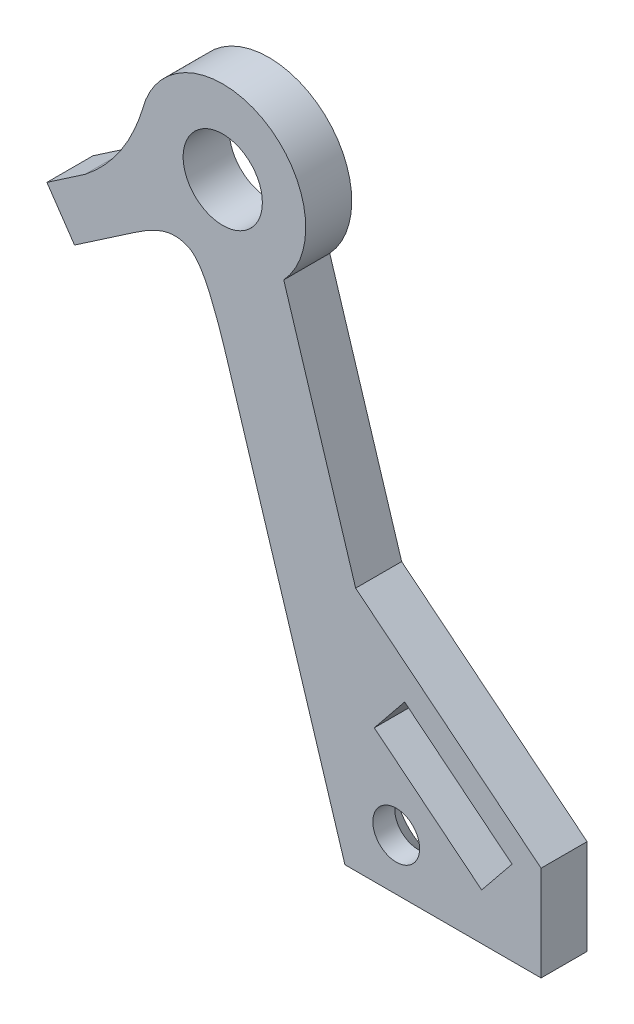
SolidWorks part; units mm, degrees
ref_plane "Front Plane" through (0, 0, 0) normal (0, 0, 1) x (1, 0, 0)
ref_plane "Top Plane" through (0, 0, 0) normal (0, 1, 0) x (1, 0, 0)
ref_plane "Right Plane" through (0, 0, 0) normal (1, 0, 0) x (0, 0, -1)
other "Right"
sketch "Sketch1" plane through (0, 0, 0) normal (0, 0, 1) x (1, 0, 0)
  line L0 (0, 10.5) -> (13, 0) construction
  line L1 (0, 0) -> (13, 0)
  line L2 (0, 0) -> (0, 10.5) construction
  line L3 (0, 10.5) -> (13, 10.5) construction
  line L4 (13, 0) -> (13, 10.5) construction
  line L5 (0, 0) -> (3.4, 0)
  line L6 (0, 0) -> (0, 3.4)
  line L7 (0, 3.4) -> (3.4, 3.4) construction
  line L8 (3.4, 0) -> (3.4, 3.4) construction
  line L9 (9.0068, 3.1288) -> (9.054, 3.1872) construction
  line L10 (9.0632, 3.0833) -> (1.945, 8.8326)
  line L11 (1.945, 8.8326) -> (3.9557, 11.322)
  line L12 (9.0632, 3.0833) -> (11.0738, 5.5728)
  line L13 (3.9557, 11.322) -> (11.0738, 5.5728)
  line L14 (0, 0) -> (-10.7241, 34.4576)
  line L15 (-10.7241, 34.4576) -> (-5.4725, 36.092)
  line L16 (-5.4725, 36.092) -> (0.7085, 16.2316)
  line L17 (0.7085, 16.2316) -> (13, 6.3039)
  line L18 (13, 0) -> (9.1103, 3.1417)
  line L19 (13, 6.3039) -> (13, 0)
  line L20 (0, 0) -> (0, 43.2357) construction
  line L21 (-8.0983, 35.2748) -> (-18.8392, 27.9513) construction
  line L22 (-17.9237, 26.6087) -> (-19.7546, 29.2939)
  line L23 (-19.7546, 29.2939) -> (-13.3551, 33.6574) construction
  line L24 (-17.9237, 26.6087) -> (-11.5242, 30.9721)
  line L25 (-19.7546, 29.2939) -> (-17.2295, 31.0156)
  line L26 (-13.4277, 36.6338) -> (-8.0983, 35.2748) construction
  circle A0 centre (3.4, 3.4) radius 1.5
  circle A1 centre (-8.0983, 35.2748) radius 2.625
  circle A3 centre (-8.0983, 35.2748) radius 5.5
  spline S0 degree 2 poles (-17.2295, 31.0156) (-14.5142, 33.1421) (-13.4277, 36.6338) knots 0 0 0 1 1 1
  spline S1 degree 3 poles (-13.9328, 29.3299) (-12.3816, 30.4078) (-10.6916, 30.7893) (-9.2236, 29.6097) (-7.8132, 25.1048) knots 0 0 0 0 0.517104 1 1 1 1
  point P28 (-18.8392, 27.9513)
  dimension "D5" = 3
  dimension "D6" = 5.25
  dimension "D7" = 11
  dimension "D26" = 6.892
  dimension "D1" = 13
  dimension "D2" = 10.5
  dimension "D3" = 3.4
  dimension "D4" = 3.4
  dimension "D8" = 51.072
  dimension "D9" = 6.3039
  dimension "D10" = 90
  dimension "D11" = 90
  dimension "D12" = 20.8
  dimension "D13" = 15.8
  dimension "D14" = 3.2
  dimension "D15" = 9.15
  dimension "D16" = 0.075
  dimension "D17" = 5
  dimension "D18" = 5.5
  dimension "D19" = 90
  dimension "D20" = 3.25
  dimension "D21" = 90
  dimension "D22" = 90
  dimension "D23" = 13
  dimension "D24" = 73
  dimension "D25" = 3.0562
  dimension "D27" = 31.593
extrude "Boss-Extrude1" add sketch "Sketch1" along normal blind 3.05 contours A3 S1 L14 L15 A1 L16 S0 | L14 A3 L16 L15 A1 | A3 L14 L1 L12 L10 L11 L13 L19 L17 L16 A0 | S0 L25 L22 L24 A3 | L24 S1 A3 | A3 S1 L14 region at (0.8388, 12.7884, 0) region at (-9.2169, 29.0135, 0) region at (-9.8194, 30.2141, 0) region at (-7.0451, 31.8908, 0) region at (-11.7561, 30.5152, 0) region at (-15.5674, 30.4807, 0)
hole_wizard "CSK for M3 Flat Head Machine Screw1" positions "Sketch2" profile "Sketch3" countersink size "M3" standard "ANSI Metric" end condition through all
sketch "Sketch2" plane through (0, 0, 3.05) normal (0, 0, 1) x (1, 0, 0)
  point P0 (3.4, 3.4)
sketch "Sketch3" plane through (3.4, 3.4, 3.05) normal (1, 0, 0) x (0, -1, 0)
  line L0 (0, 0) -> (0, 3.05)
  line L1 (0, 3.05) -> (1.55, 3.05)
  line L2 (1.55, 3.05) -> (1.55, 1.6)
  line L3 (1.55, 1.6) -> (3.15, 0)
  line L5 (3.15, 0) -> (0, 0)
  line L6 (-1.55, 1.6) -> (-3.15, 0) construction
  line L11 (0, -6.35) -> (0, 107.95) construction
  dimension "Thru Hole Dia." = 3.1
  dimension "Thru Hole Depth" = 3.05
  dimension "Near C'Sink Dia." = 6.3
  dimension "Near C'Sink Angle" = 90
mirror "Mirror1" about plane through (0, 0, 0) normal (0, 0, 1) of bodies 103
delete or keep bodies "Body-Delete/Keep 1" type delete bodies bodies 103
